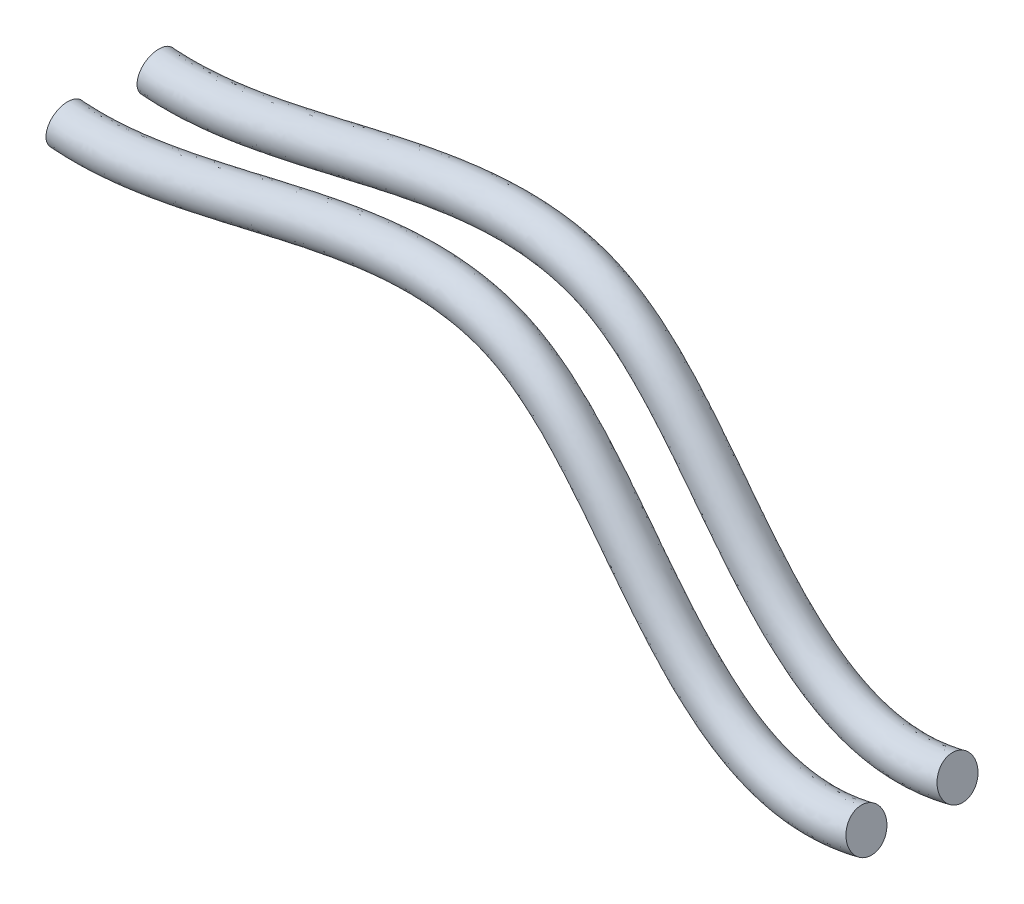
SolidWorks part; units mm, degrees
ref_plane "Спереди" through (0, 0, 0) normal (0, 0, 1) x (1, 0, 0)
ref_plane "Сверху" through (0, 0, 0) normal (0, 1, 0) x (1, 0, 0)
ref_plane "Справа" through (0, 0, 0) normal (1, 0, 0) x (0, 0, -1)
sketch "Эскиз1" plane through (0, 0, 0) normal (0, 0, 1) x (1, 0, 0)
  line L1 (-45.1219, -19.9026) -> (-35.1683, -18.9398)
  line L2 (-35.1683, -18.9398) -> (-10.2232, -17.2849)
  line L3 (-10.2232, -17.2849) -> (7.3741, -35.0426)
  line L4 (7.3741, -35.0426) -> (17.281, -36.4039)
  spline S0 degree 3 poles (-45.1219, -19.9026) (-34.409, -20.8102) (-4.9031, -4.1469) (3.3227, -40.0357) (17.281, -36.4039) knots 0 0 0 0 0.5 1 1 1 1
  dimension "D1" = 10
  dimension "D2" = 25
  dimension "D3" = 25
  dimension "D4" = 10
ref_plane "Плоскость1" through (-45.1219, -19.9026, 0) normal (0.9964, -0.0844, 0) x (0, 0, -1)
sketch "Эскиз2" plane through (-45.1219, -19.9026, 0) normal (0.9964, -0.0844, 0) x (0, 0, -1)
  line L0 (0, 0) -> (-7.1661, 0) construction
  circle A0 centre (0, 0) radius 1.55
  circle A1 centre (-7.1, 0) radius 1.55
  dimension "D1" = 3.1
  dimension "D2" = 3.1
  dimension "D3" = 7.1
sweep "По траектории1" add profiles "Эскиз2" path "Эскиз1"
